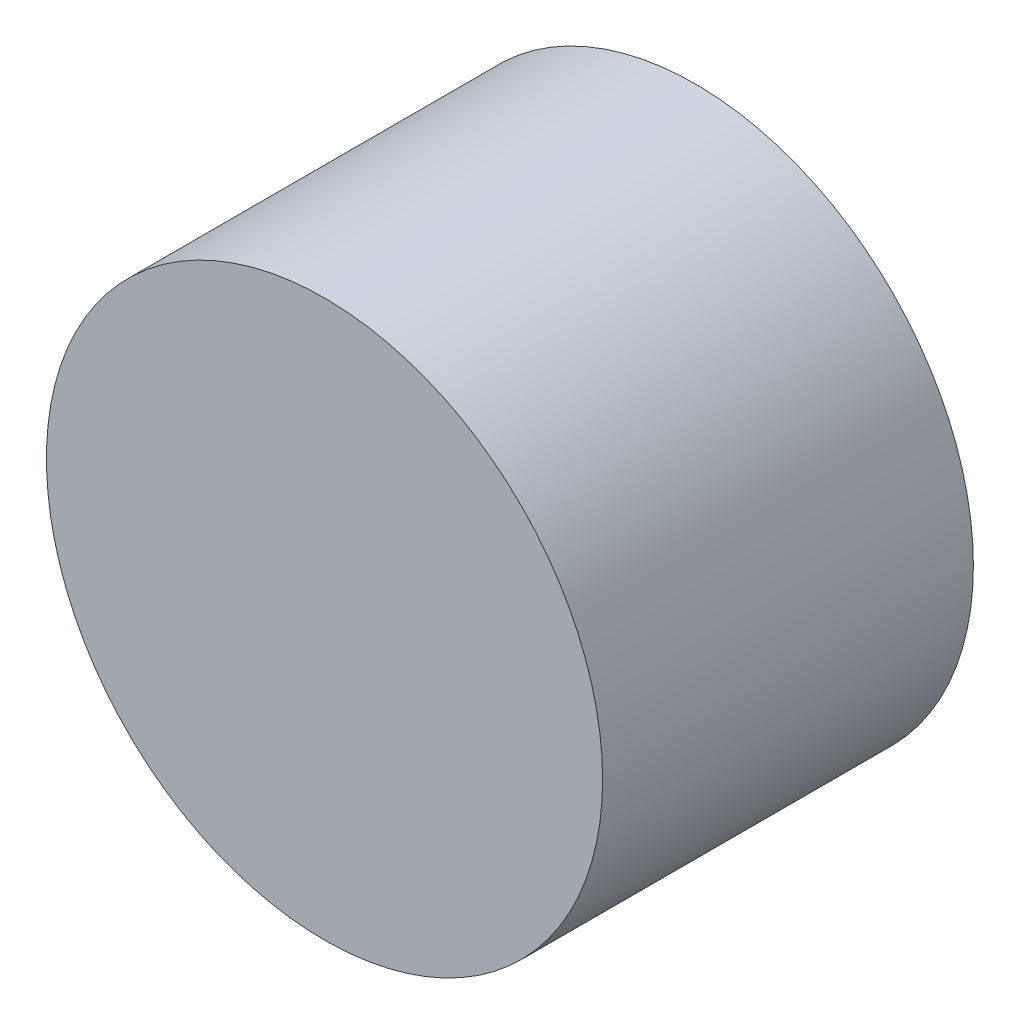
SolidWorks part; units mm, degrees
ref_plane "Front Plane" through (0, 0, 0) normal (0, 0, 1) x (1, 0, 0)
ref_plane "Top Plane" through (0, 0, 0) normal (0, 1, 0) x (1, 0, 0)
ref_plane "Right Plane" through (0, 0, 0) normal (1, 0, 0) x (0, 0, -1)
sketch "Sketch1" plane through (0, 0, 0) normal (0, 0, 1) x (1, 0, 0)
  circle A0 centre (0, 0) radius 4.25
  circle A1 centre (0, 0) radius 6
  dimension "D1" = 8.5
  dimension "D2" = 12
extrude "Boss-Extrude1" add sketch "Sketch1" along normal blind 8 contours A0 | A1 A0 region at (0, 0, 0) region at (-5.8303, 0, 0)
extrude "Cut-Extrude1" cut sketch "Sketch1<4>" along normal blind 5.5 contours A0
sketch "Sketch1<4>" plane through (0, 0, 0) normal (0, 0, 1) x (1, 0, 0) same geometry as "Sketch1"
